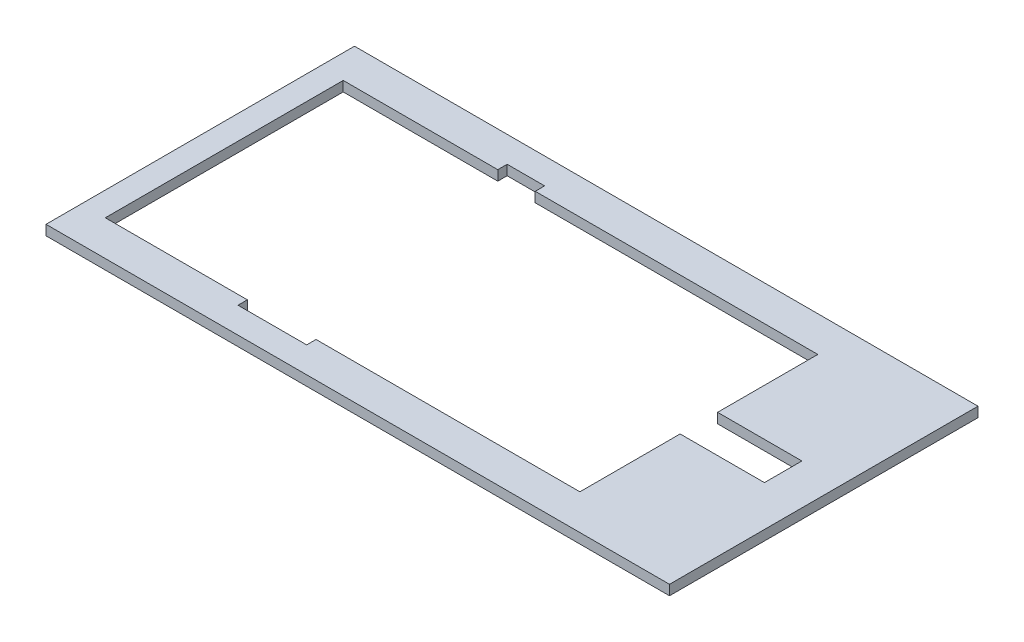
SolidWorks part; units mm, degrees
ref_plane "Front Plane" through (0, 0, 0) normal (0, 0, 1) x (1, 0, 0)
ref_plane "Top Plane" through (0, 0, 0) normal (0, 1, 0) x (1, 0, 0)
ref_plane "Right Plane" through (0, 0, 0) normal (1, 0, 0) x (0, 0, -1)
sketch "Sketch1" plane through (0, 0, 0) normal (0, 1, 0) x (1, 0, 0)
  line L0 (-45.0857, 15.8191) -> (4.4143, 15.8191)
  line L1 (-52.7757, 27.1191) -> (146.9143, 27.1191)
  line L2 (-52.7757, 27.1191) -> (-52.7757, -71.6809)
  line L3 (-52.7757, -71.6809) -> (146.9143, -71.6809)
  line L4 (146.9143, 27.1191) -> (146.9143, -71.6809)
  line L5 (106.9143, 15.8191) -> (106.9143, -16.2809)
  line L6 (106.9143, -16.2809) -> (133.9143, -16.2809)
  line L7 (133.9143, -16.2809) -> (133.9143, -28.2809)
  line L8 (133.9143, -28.2809) -> (106.9143, -28.2809)
  line L9 (106.9143, -28.2809) -> (106.9143, -60.3809)
  line L10 (106.9143, -60.3809) -> (22.4143, -60.3809)
  line L11 (-45.0857, -60.3809) -> (-45.0857, 15.8191)
  line L12 (4.4143, 15.8191) -> (4.4143, 18.8191)
  line L13 (4.4143, 18.8191) -> (16.4143, 18.8191)
  line L14 (16.4143, 18.8191) -> (16.4143, 15.8191)
  line L15 (16.4143, 15.8191) -> (106.9143, 15.8191)
  line L16 (0.4143, -60.3809) -> (0.4143, -63.3809)
  line L17 (0.4143, -63.3809) -> (22.4143, -63.3809)
  line L18 (22.4143, -63.3809) -> (22.4143, -60.3809)
  line L19 (0.4143, -60.3809) -> (-45.0857, -60.3809)
  dimension "D1" = 199.69
  dimension "D2" = 98.8
  dimension "D3" = 76.2
  dimension "D4" = 11.3
  dimension "D5" = 152
  dimension "D6" = 12
  dimension "D7" = 27
  dimension "D8" = 32.1
  dimension "D9" = 40
  dimension "D10" = 3
  dimension "D11" = 12
  dimension "D12" = 49.5
  dimension "D13" = 3
  dimension "D14" = 22
  dimension "D15" = 45.5
extrude "Boss-Extrude1" add sketch "Sketch1" along normal blind 3.2
equation "\"Fit\"= 1"
equation "\"cover width\"= 98.8"
equation "\"top phone insert length\" = 199.69"
equation "\"thinner acrylic\"= 3.2"
equation "\"D1@Sketch1\"=\"top phone insert length\""
equation "\"D2@Sketch1\"=\"cover width\""
equation "\"D1@Boss-Extrude1\"=\"thinner acrylic\""
equation "\"phone edge to bottom\" = 40"
equation "\"charge cable width\"= 12"
equation "\"charge cable length\"= 27"
equation "\"phone width\"= 76.2"
equation "\"phone length\"= 152"
equation "\"D3@Sketch1\"=\"phone width\""
equation "\"D4@Sketch1\"=(\"cover width\"-\"phone width\")/2"
equation "\"D5@Sketch1\"=\"phone length\""
equation "\"D6@Sketch1\"=\"charge cable width\""
equation "\"D7@Sketch1\"=\"charge cable length\""
equation "\"D8@Sketch1\"=(\"phone width\"-\"charge cable width\")/2"
equation "\"D9@Sketch1\"=\"phone edge to bottom\""
equation "\"button depth\"= 3"
equation "\"volume button length\" = 22"
equation "\"power button length\"= 12"
equation "\"power button from top\"= 49.5"
equation "\"volume button from top\" = 45.5"
equation "\"D10@Sketch1\"=\"button depth\""
equation "\"D11@Sketch1\"=\"power button length\""
equation "\"D12@Sketch1\"=\"power button from top\""
equation "\"D13@Sketch1\"=\"button depth\""
equation "\"D14@Sketch1\"=\"volume button length\""
equation "\"D15@Sketch1\"=\"volume button from top\""
